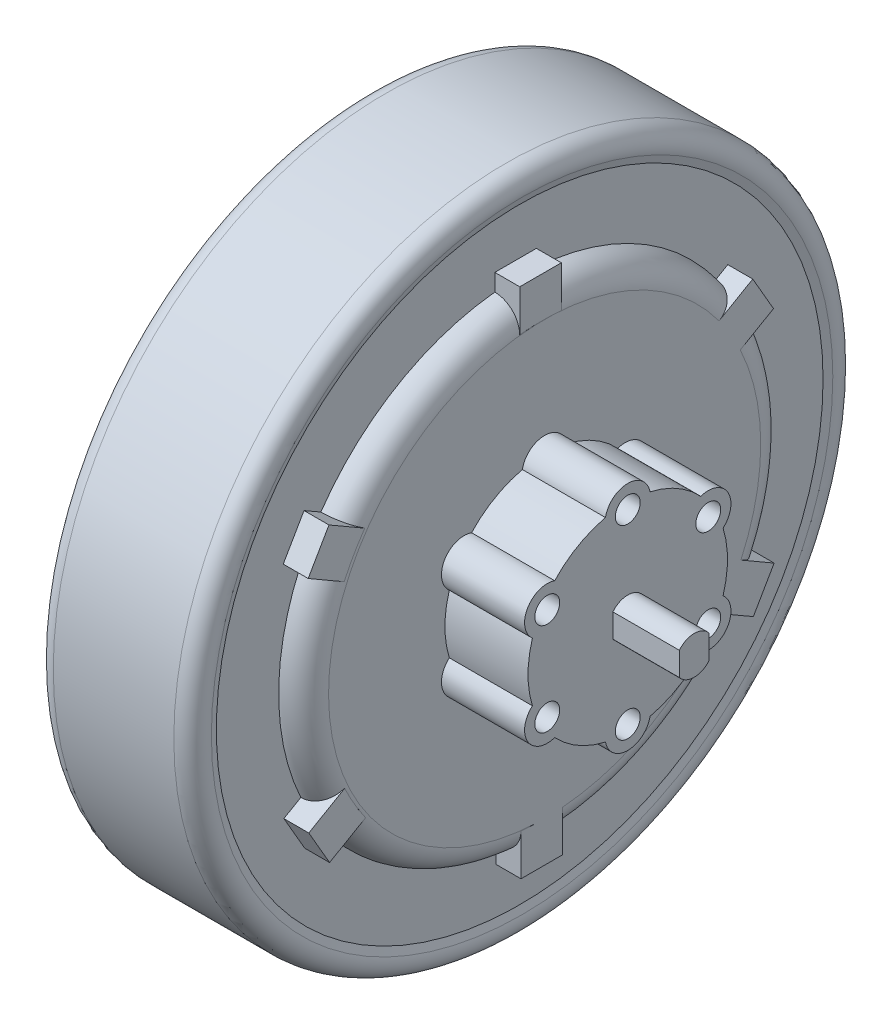
SolidWorks part; units mm, degrees
ref_plane "Front Plane" through (0, 0, 0) normal (0, 0, 1) x (1, 0, 0)
ref_plane "Top Plane" through (0, 0, 0) normal (0, 1, 0) x (1, 0, 0)
ref_plane "Right Plane" through (0, 0, 0) normal (1, 0, 0) x (0, 0, -1)
sketch "Sketch1" plane through (0, 0, 0) normal (0, 1, 0) x (1, 0, 0)
  line L0 (0, 0) -> (0, 89.9577) construction
  line L1 (-25.4, 89.9577) -> (25.4, 89.9577)
  line L2 (25.4, 89.9577) -> (22.528, 81.0677)
  line L3 (22.528, 81.0677) -> (22.528, 62.0177)
  line L4 (22.528, 62.0177) -> (30.148, 62.0177)
  line L5 (30.148, 62.0177) -> (30.148, 18.8377)
  line L6 (27.9161, -11.6423) -> (-27.9161, -11.6423)
  line L7 (0, -11.6423) -> (0, 89.9577)
  line L8 (30.148, 62.0177) -> (30.148, 68.7262) construction
  line L9 (30.148, 18.8377) -> (55.548, 18.8377)
  line L10 (55.548, 18.8377) -> (55.548, -11.6423)
  line L11 (55.548, -11.6423) -> (27.9161, -11.6423)
  line L12 (-30.148, 62.0177) -> (-30.148, 68.7262) construction
  line L13 (-30.148, -11.6423) -> (-27.9161, -11.6423)
  line L16 (-30.148, 62.0177) -> (-30.148, 18.8377)
  line L17 (-22.528, 62.0177) -> (-30.148, 62.0177)
  line L18 (-22.528, 81.0677) -> (-22.528, 62.0177)
  line L19 (-25.4, 89.9577) -> (-22.528, 81.0677)
  line L21 (-30.1884, -2.7523) -> (-36.5384, -2.7523)
  line L22 (-36.5384, -2.7523) -> (-36.5384, -4.5696)
  line L23 (-36.5384, -11.6423) -> (-30.148, -11.6423)
  line L24 (-30.1884, -2.7523) -> (-30.148, 18.8377)
  line L25 (-36.5384, -4.5696) -> (-38.4853, -4.5696)
  line L26 (-38.4853, -4.5696) -> (-38.4853, -11.6423)
  line L27 (-38.4853, -11.6423) -> (-36.5384, -11.6423)
  dimension "D1" = 101.6
  dimension "D2" = 8.89
  dimension "D3" = 19.05
  dimension "D4" = 7.62
  dimension "D5" = 90
  dimension "D6" = 25.4
  dimension "D7" = 6.35
  dimension "D8" = 25.4
  dimension "D9" = 71.12
  dimension "D10" = 8.89
revolve "Revolve1" add sketch "Sketch1" angle 360 about L6
ref_plane "Plane1" through (55.548, 0, 0) normal (1, 0, 0) x (0, 0, -1)
fillet "Fillet1" radius 7.62 2 edges at (30.148, 0, -62.0177) (-30.148, 0, -62.0177)
ref_plane "Plane2" through (-30.148, 0, 0) normal (-1, 0, 0) x (0, 0, 1)
sketch "Sketch3" plane through (-30.148, 0, 0) normal (-1, 0, 0) x (0, 0, 1)
  line L0 (6.5481, 65.8481) -> (6.5481, 78.4819)
  line L1 (6.5481, 78.4819) -> (19.2481, 78.4819)
  line L2 (19.2481, 78.4819) -> (19.2481, 65.7819)
  line L3 (12.8981, 30.4541) -> (12.8981, 78.4819) construction
  line L4 (83.9057, 33.5987) -> (72.9072, 27.2487)
  line L5 (77.5557, 44.5973) -> (83.9057, 33.5987)
  line L6 (66.6145, 38.2803) -> (77.5557, 44.5973)
  line L7 (77.3646, -44.838) -> (66.366, -38.488)
  line L8 (83.7146, -33.8395) -> (77.3646, -44.838)
  line L9 (72.7734, -27.5226) -> (83.7146, -33.8395)
  line L10 (6.1658, -78.3916) -> (6.1658, -65.6916)
  line L11 (18.8658, -78.3916) -> (6.1658, -78.3916)
  line L12 (18.8658, -65.7578) -> (18.8658, -78.3916)
  line L13 (-58.4919, -33.5084) -> (-47.4933, -27.1584)
  line L14 (-52.1419, -44.5069) -> (-58.4919, -33.5084)
  line L15 (-41.2006, -38.19) -> (-52.1419, -44.5069)
  line L16 (-51.9507, 44.9283) -> (-40.9522, 38.5783)
  line L17 (-58.3007, 33.9298) -> (-51.9507, 44.9283)
  line L18 (-47.3595, 27.6129) -> (-58.3007, 33.9298)
  circle A0 centre (11.6423, 0) radius 66.04 construction
  circle A1 centre (11.6423, 0) radius 30.48 construction
  circle A2 centre (11.6423, 0) radius 30.48 construction
  arc A3 (6.5481, 65.8481) -> (19.2481, 65.7819) centre (12.5157, -7.5698) cw
  arc A4 (66.6145, 38.2803) -> (72.9072, 27.2487) centre (6.0166, -3.5967) cw
  arc A5 (72.7734, -27.5226) -> (66.366, -38.488) centre (6.2078, 4.0183) cw
  arc A6 (18.8658, -65.7578) -> (6.1658, -65.6916) centre (12.8982, 7.6601) cw
  arc A7 (-41.2006, -38.19) -> (-47.4933, -27.1584) centre (19.3973, 3.687) cw
  arc A8 (-47.3595, 27.6129) -> (-40.9522, 38.5783) centre (19.206, -3.9279) cw
  point P41 (12.7069, 0.0452)
  dimension "D1" = 12.7
  dimension "D2" = 12.7
  dimension "D3" = 6
extrude "Boss-Extrude1" add sketch "Sketch3" against normal up to next
ref_plane "Plane3" through (0, 10.8699, 6.2757) normal (0, 0.866, 0.5) x (1, 0, 0)
sketch "Sketch5" plane through (0, 10.8699, 6.2757) normal (0, 0.866, 0.5) x (1, 0, 0)
  line L0 (-55.548, -10.0826) -> (-84.4313, -10.0826) construction
  line L1 (-55.548, 20.3974) -> (-55.548, -40.5626) construction
  line L2 (-30.4898, -79.7792) -> (-23.3898, -90.3477)
  line L5 (-23.3898, -90.3477) -> (-30.4898, -90.3477)
  line L6 (-30.4898, -90.3477) -> (-30.4898, -79.7792)
  point P6 (0, 0)
mirror "Mirror1" about plane through (0, 0, 0) normal (1, 0, 0) of "Boss-Extrude1"
sketch "Sketch7" plane through (55.548, 0, 0) normal (1, 0, 0) x (0, 0, -1)
  arc A0 (-18.451, 29.7098) -> (-4.8337, 29.7098) centre (-11.6423, 28.4042) cw
  circle A1 centre (-11.6423, 0) radius 30.48 construction
  arc A2 (-18.451, 29.7098) -> (-4.8337, 29.7098) centre (-11.6423, 0) cw
  arc A3 (10.6828, 20.7514) -> (17.4914, 8.9584) centre (-11.6423, 0) cw
  arc A4 (10.6828, 20.7514) -> (17.4914, 8.9584) centre (12.9564, 14.2021) cw
  arc A5 (17.4914, -8.9584) -> (10.6828, -20.7514) centre (-11.6423, 0) cw
  arc A6 (17.4914, -8.9584) -> (10.6828, -20.7514) centre (12.9564, -14.2021) cw
  arc A7 (-4.8337, -29.7098) -> (-18.451, -29.7098) centre (-11.6423, 0) cw
  arc A8 (-4.8337, -29.7098) -> (-18.451, -29.7098) centre (-11.6423, -28.4042) cw
  arc A9 (-33.9675, -20.7514) -> (-40.7761, -8.9584) centre (-11.6423, 0) cw
  arc A10 (-33.9675, -20.7514) -> (-40.7761, -8.9584) centre (-36.2411, -14.2021) cw
  arc A11 (-40.7761, 8.9584) -> (-33.9675, 20.7514) centre (-11.6423, 0) cw
  arc A12 (-40.7761, 8.9584) -> (-33.9675, 20.7514) centre (-36.2411, 14.2021) cw
  point P24 (-11.6423, 0)
  dimension "D1" = 6
extrude "Boss-Extrude2" add sketch "Sketch7" against normal up to next
sketch "Sketch8" plane through (55.548, 0, 0) normal (1, 0, 0) x (0, 0, -1)
  circle A0 centre (-11.6423, 28.4042) radius 3.81
  circle A1 centre (12.9564, 14.2021) radius 3.81
  circle A2 centre (12.9564, -14.2021) radius 3.81
  circle A3 centre (-11.6423, -28.4042) radius 3.81
  circle A4 centre (-36.2411, -14.2021) radius 3.81
  circle A5 centre (-36.2411, 14.2021) radius 3.81
  point P16 (-11.6423, 0)
  dimension "D1" = 6
extrude "Cut-Extrude1" cut sketch "Sketch8" against normal blind 10.16
sketch "Sketch9" plane through (55.548, 0, 0) normal (1, 0, 0) x (0, 0, -1)
  line L0 (-7.0958, 3.6076) -> (-7.0958, -3.6076)
  line L1 (-11.6423, 0) -> (-11.6423, 3.0278) construction
  line L2 (-16.1889, 3.6076) -> (-16.1889, -3.6076)
  arc A0 (-16.1889, -3.6076) -> (-7.0958, -3.6076) centre (-11.6423, 0) ccw
  arc A1 (-7.0958, 3.6076) -> (-16.1889, 3.6076) centre (-11.6423, 0) ccw
  dimension "D1" = 11.6078
extrude "Boss-Extrude3" add sketch "Sketch9" along normal blind 50.8 from offset 30.48 offset against normal yes
mirror "Mirror3" about plane through (0, 0, 0) normal (1, 0, 0) of "Boss-Extrude3"
fillet "Fillet2" radius 5.08 2 edges at (-25.4, 0, -89.9577) (25.4, 0, -89.9577)
sketch "Sketch10" plane through (0, 0, 0) normal (0, 0, 1) x (1, 0, 0)
  line L1 (-86.9993, 14.1566) -> (-59.5673, 14.1566)
  line L2 (-86.9993, 14.1566) -> (-86.9993, -9.7028)
  line L3 (-86.9993, -9.7028) -> (-59.5673, -9.7028)
  line L4 (-59.5673, 14.1566) -> (-59.5673, -9.7028)
  line L5 (-86.9993, 14.1566) -> (-59.5673, -9.7028) construction
  line L6 (-86.9993, -9.7028) -> (-59.5673, 14.1566) construction
  point P4 (-73.2833, 2.2269)
  dimension "D1" = 27.432
extrude "Cut-Extrude2" cut sketch "Sketch10" against normal through all both and the other way through all
